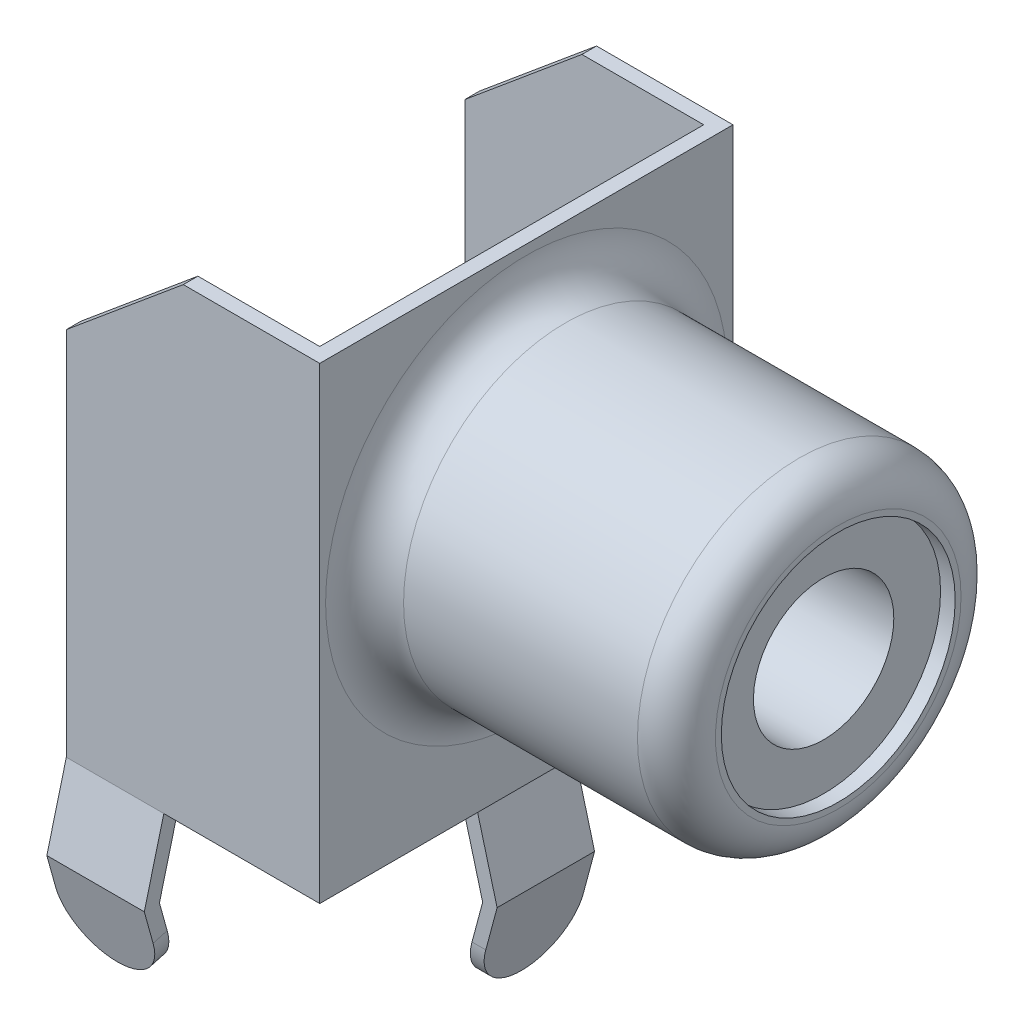
SolidWorks part; units mm, degrees
ref_plane "Front" through (0, 0, 0) normal (0, 0, 1) x (1, 0, 0)
ref_plane "Top" through (0, 0, 0) normal (0, 1, 0) x (1, 0, 0)
ref_plane "Right" through (0, 0, 0) normal (1, 0, 0) x (0, 0, -1)
sketch "Sketch1" plane through (0, 0, 0) normal (1, 0, 0) x (0, 0, -1)
  line L0 (0, 0) -> (0, 17.5966) construction
  line L1 (5.3, 5.4) -> (-5.3, 5.4)
  line L2 (-5.3, 5.4) -> (-5.3, -6.6)
  line L3 (-5.3, -6.6) -> (5.3, -6.6)
  line L4 (5.3, 5.4) -> (5.3, -6.6)
  line L5 (1.25, -9.55) -> (1.25, -6.6)
  line L6 (-1.25, -9.55) -> (-1.25, -6.6)
  line L7 (-5.3, -6.6) -> (-5.8, -8.5327)
  line L8 (4.3187, -10.8) -> (-5.8789, -10.8) construction
  line L9 (-5.8, -8.5327) -> (-5.2407, -10.55)
  line L10 (-5.2407, -10.55) -> (-4.8794, -10.4498)
  line L11 (-4.8794, -10.4498) -> (-5.4118, -8.5294)
  line L12 (-5.4118, -8.5294) -> (-4.9127, -6.6)
  line L13 (5.4118, -8.5294) -> (4.9127, -6.6)
  line L14 (4.8794, -10.4498) -> (5.4118, -8.5294)
  line L15 (5.2407, -10.55) -> (4.8794, -10.4498)
  line L16 (5.8, -8.5327) -> (5.2407, -10.55)
  line L17 (5.3, -6.6) -> (5.8, -8.5327)
  line L18 (-4.9127, -6.6) -> (-4.9127, 5.4)
  line L19 (4.9127, -6.6) -> (4.9127, 5.4)
  line L20 (-0.65, -9.8) -> (0.65, -9.8)
  line L21 (0.65, -9.8) -> (0.65, -5.455)
  line L22 (0.65, -5.455) -> (1.625, -4.48)
  line L23 (1.625, -4.48) -> (1.625, -1.6)
  line L24 (1.625, -1.6) -> (-1.625, -1.6)
  line L25 (0, 0) -> (0, -11.7366) construction
  line L26 (-1.625, -4.48) -> (-1.625, -1.6)
  line L27 (-0.65, -5.455) -> (-1.625, -4.48)
  line L28 (-0.65, -9.8) -> (-0.65, -5.455)
  line L29 (-4.8794, -10.4498) -> (4.8794, -10.4498)
  line L30 (-1.625, -1.975) -> (1.625, -1.975)
  circle A0 centre (0, 0) radius 1.8
  circle A1 centre (0, 0) radius 4.15
  arc A2 (-1.25, -9.55) -> (1.25, -9.55) centre (0, -9.55) ccw
  circle A3 centre (0, 0) radius 3.8125
  circle A4 centre (0, 0) radius 3.775
  circle A5 centre (0, 0) radius 3
  point P10 (0, 5.4)
  point P11 (0, -6.6)
  point P38 (0, -1.6)
  dimension "D1" = 3.6
  dimension "D2" = 8.3
  dimension "D7" = 4.2
  dimension "D17" = 7.625
  dimension "D19" = 6
  dimension "D3" = 10.6
  dimension "D4" = 12
  dimension "D5" = 6.6
  dimension "D6" = 2.5
  dimension "D8" = 3.95
  dimension "D9" = 0.375
  dimension "D10" = 0.375
  dimension "D11" = 11.6
  dimension "D12" = 150
  dimension "D13" = 1.6
  dimension "D14" = 3.25
  dimension "D15" = 2.88
  dimension "D16" = 135
  dimension "D20" = 0.375
  dimension "D21" = 1.3
  dimension "D22" = 3.2
  dimension "D18" = 0.375
sketch "Sketch2" plane through (0, 0, 0) normal (0, 0, 1) x (1, 0, 0)
  line L0 (0, 0) -> (0, 19.9245)
  line L1 (0, 19.9245) -> (6.5, 19.9245)
  line L2 (6.5, 19.9245) -> (6.5, 15.5349)
  line L3 (6.5, 15.5349) -> (14.5, 15.5349)
  line L4 (14.5, 15.5349) -> (14.5, 0)
  line L5 (14.125, 15.5349) -> (14.125, 0)
  line L6 (1.25, 19.9245) -> (1.25, 0)
  line L7 (6.5, -6.6) -> (7, -8.466)
  line L8 (7, -8.466) -> (6.4416, -10.55)
  line L9 (6.4416, -10.55) -> (6.1118, -10.4616)
  line L10 (6.1118, -10.4616) -> (6.6291, -8.5308)
  line L11 (6.6291, -8.5308) -> (6.1118, -6.6)
  line L12 (6.1118, -6.6) -> (6.5, -6.6)
  line L13 (0, -6.6) -> (0, -9.3)
  line L16 (2.5, -9.3) -> (2.5, -6.6)
  line L17 (2.5, -6.6) -> (0, -6.6)
  arc A0 (0, -9.3) -> (2.5, -9.3) centre (1.25, -9.3) ccw
  dimension "D11" = 2.5
  dimension "D1" = 6.5
  dimension "D2" = 14.5
  dimension "D3" = 0.375
  dimension "D4" = 1.25
  dimension "D5" = 6.6
  dimension "D6" = 0.5
  dimension "D7" = 0.375
  dimension "D8" = 3.95
  dimension "D9" = 6.5
  dimension "D10" = 150
  dimension "D12" = 2.7
ref_axis "Axis1" through (-80.9, 0, 0) along (1, 0, 0)
sketch "Sketch22" plane through (0, 0, 0) normal (1, 0, 0) x (0, 0, -1)
  line L1 (5.3, 5.4) -> (5.3, -6.6) construction
  line L2 (5.3, 5.4) -> (-5.3, 5.4) construction
  line L3 (-5.3, 5.4) -> (-5.3, -6.6) construction
  line L4 (-5.3, -6.6) -> (-5.8, -8.5327) construction
  line L5 (5.3, 5.4) -> (5.3, -6.6)
  line L6 (5.3, 5.4) -> (-5.3, 5.4)
  line L7 (-5.3, 5.4) -> (-5.3, -6.6)
  line L8 (-5.8, -8.5327) -> (-5.2407, -10.55) construction
  line L9 (-5.2407, -10.55) -> (-4.8794, -10.4498) construction
  line L10 (-4.8794, -10.4498) -> (4.8794, -10.4498) construction
  line L11 (5.2407, -10.55) -> (4.8794, -10.4498) construction
  line L12 (5.8, -8.5327) -> (5.2407, -10.55) construction
  line L13 (5.3, -6.6) -> (5.8, -8.5327) construction
  line L14 (-5.3, -6.6) -> (-5.8, -8.5327)
  line L15 (-5.8, -8.5327) -> (-5.2407, -10.55)
  line L16 (-5.2407, -10.55) -> (-4.8794, -10.4498)
  line L17 (-4.8794, -10.4498) -> (4.8794, -10.4498)
  line L18 (5.2407, -10.55) -> (4.8794, -10.4498)
  line L19 (5.8, -8.5327) -> (5.2407, -10.55)
  line L20 (5.3, -6.6) -> (5.8, -8.5327)
extrude "Extrude15" add sketch "Sketch22" along normal up to vertex (6.5 mm away) up to point (6.5, 15.5349, 0)
shell "Shell1" thickness 0.375 removed face at (3.25, 5.4, 0) removed face at (3.25, -10.4498, 0) removed face at (0, -6.1465, 0)
sketch "Sketch23" plane through (6.5, 0, 0) normal (1, 0, 0) x (0, 0, -1)
  line L0 (5.4118, -8.5294) -> (4.9127, -6.6) construction
  line L1 (4.8794, -10.4498) -> (5.4118, -8.5294) construction
  line L2 (-4.8794, -10.4498) -> (4.8794, -10.4498) construction
  line L3 (-4.8794, -10.4498) -> (-5.4118, -8.5294) construction
  line L4 (-5.4118, -8.5294) -> (-4.9127, -6.6) construction
  line L5 (-5.3, -6.6) -> (5.3, -6.6) construction
  line L6 (5.4118, -8.5294) -> (4.9127, -6.6)
  line L7 (4.8794, -10.4498) -> (5.4118, -8.5294)
  line L8 (-4.8794, -10.4498) -> (4.8794, -10.4498)
  line L9 (-4.8794, -10.4498) -> (-5.4118, -8.5294)
  line L10 (-5.4118, -8.5294) -> (-4.9127, -6.6)
  line L11 (-4.9127, -6.6) -> (4.9127, -6.6)
extrude "Cut-Extrude1" cut sketch "Sketch23" against normal through all
sketch "Sketch24" plane through (0, 0, 0) normal (0, 0, 1) x (1, 0, 0)
  line L0 (6.6291, -8.5308) -> (6.1118, -6.6) construction
  line L1 (6.1118, -6.6) -> (6.5, -6.6) construction
  line L2 (6.5, -6.6) -> (7, -8.466) construction
  line L3 (7, -8.466) -> (6.4416, -10.55) construction
  line L4 (6.1118, -10.4616) -> (6.6291, -8.5308) construction
  line L6 (6.6291, -8.5308) -> (6.1118, -6.6)
  line L7 (6.1118, -6.6) -> (6.5, -6.6)
  line L8 (6.5, -6.6) -> (7, -8.466)
  line L9 (7, -8.466) -> (6.2097, -11.4156)
  line L10 (5.8632, -11.3894) -> (6.6291, -8.5308)
  line L11 (6.2097, -11.4156) -> (5.8632, -11.3894)
extrude "Extrude16" add sketch "Sketch24" along normal up to vertex (1.25 mm away) and the other way up to vertex (1.25 mm away) separate body up to point (0, -9.55, 1.25) other way up to point (0, -9.55, -1.25)
sketch "Sketch28" plane through (0, -2.1022, 7.5828) normal (0, -0.2672, 0.9637) x (1, 0, 0)
  line L1 (2.5, -6.673) -> (8.1659, -6.673)
  line L3 (0, -6.3601) -> (0, -8.962)
  line L4 (2.5, -6.3601) -> (0, -6.3601)
  line L5 (2.5, -8.962) -> (2.5, -6.3601)
  line L6 (0, -6.673) -> (0, -7.5164)
  line L7 (8.1659, -6.673) -> (8.1659, -10.1113)
  line L8 (2.5, -7.5164) -> (2.5, -6.673)
  line L9 (8.1659, -10.1113) -> (-0.8346, -10.1113)
  line L10 (-0.8346, -10.1113) -> (-0.8346, -6.673)
  line L11 (-0.8346, -6.673) -> (0, -6.673)
  arc A1 (0, -7.5164) -> (2.5, -7.5164) centre (1.25, -7.5164) ccw
  ellipse E1 centre (1.25, -8.962) end of major axis (2.5, -8.962) minor radius 1.2046 (0, -8.962) -> (2.5, -8.962) ccw
  dimension "D1" = 0
extrude "Cut-Extrude5" cut sketch "Sketch28" against normal up to surface (0.375 mm away)
sketch "Sketch30" plane through (0, -2.1022, -7.5828) normal (0, -0.2672, -0.9637) x (-1, 0, 0)
  line L0 (-2.5, -6.673) -> (-6.7238, -6.673)
  line L2 (-6.5, -8.7664) -> (0, -8.7664) construction
  line L3 (0, -8.962) -> (0, -6.3601)
  line L4 (0, -6.3601) -> (-2.5, -6.3601)
  line L5 (-2.5, -6.3601) -> (-2.5, -8.962)
  line L6 (0, -7.5164) -> (0, -6.673)
  line L7 (-6.7238, -6.673) -> (-6.7238, -9.6775)
  line L8 (-2.5, -6.673) -> (-2.5, -7.5164)
  line L9 (-2.5, -8.7664) -> (0, -8.7664) construction
  line L10 (-6.7238, -9.6775) -> (1.0431, -9.6775)
  line L11 (1.0431, -9.6775) -> (1.0431, -6.673)
  line L12 (1.0431, -6.673) -> (0, -6.673)
  arc A0 (-2.5, -7.5164) -> (0, -7.5164) centre (-1.25, -7.5164) ccw
  ellipse E1 centre (-1.25, -8.962) end of major axis (-2.5, -8.962) minor radius 1.2046 (-2.5, -8.962) -> (0, -8.962) ccw
  dimension "D1" = 0
extrude "Cut-Extrude6" cut sketch "Sketch30" against normal up to surface (0.375 mm away)
sketch "Sketch31" plane through (6.5, 0, 0) normal (1, 0, 0) x (0, 0, -1)
  line L0 (5.2407, -10.55) -> (4.8794, -10.4498) construction
  line L1 (5.8, -8.5327) -> (5.2407, -10.55) construction
  line L2 (5.3, -6.6) -> (5.8, -8.5327) construction
  line L3 (5.4118, -8.5294) -> (4.9127, -6.6) construction
  line L4 (4.8794, -10.4498) -> (5.4118, -8.5294) construction
  line L5 (-5.8, -8.5327) -> (-5.2407, -10.55) construction
  line L6 (-5.2407, -10.55) -> (-4.8794, -10.4498) construction
  line L7 (-4.8794, -10.4498) -> (-5.4118, -8.5294) construction
  line L8 (-5.3, -6.6) -> (5.3, -6.6) construction
  line L9 (-5.4118, -8.5294) -> (-4.9127, -6.6) construction
  line L10 (-5.3, -6.6) -> (-5.8, -8.5327) construction
  line L11 (5.2407, -10.55) -> (4.8794, -10.4498)
  line L12 (5.8, -8.5327) -> (5.2407, -10.55)
  line L13 (5.3, -6.6) -> (5.8, -8.5327)
  line L14 (5.4118, -8.5294) -> (4.9127, -6.6)
  line L15 (4.8794, -10.4498) -> (5.4118, -8.5294)
  line L16 (-5.8, -8.5327) -> (-5.2407, -10.55)
  line L17 (-5.2407, -10.55) -> (-4.8794, -10.4498)
  line L18 (-4.8794, -10.4498) -> (-5.4118, -8.5294)
  line L19 (-5.3, -6.6) -> (-4.9127, -6.6)
  line L20 (-5.4118, -8.5294) -> (-4.9127, -6.6)
  line L21 (-5.3, -6.6) -> (-5.8, -8.5327)
  line L22 (4.9127, -6.6) -> (5.3, -6.6)
extrude "Cut-Extrude7" cut sketch "Sketch31" against normal blind 4
sketch "Sketch32" plane through (6.5, 1.6977, 0) normal (1, 0, 0) x (0, 0, -1)
  arc A0 (-1.25, -11.2477) -> (1.25, -11.2477) centre (0, -11.2477) ccw construction
  arc A1 (-1.25, -11.2477) -> (1.25, -11.2477) centre (0, -11.2477) ccw
extrude "Cut-Extrude8" cut sketch "Sketch32" against normal through all and the other way through all flip side to cut
sketch "Sketch33" plane through (6.5, 0, 0) normal (1, 0, 0) x (0, 0, -1)
  circle A0 centre (0, 0) radius 3.8125 construction
  circle A1 centre (0, 0) radius 3.8125
extrude "Cut-Extrude9" cut sketch "Sketch33" against normal through all
sketch "Sketch34" plane through (6.5, 0, 0) normal (1, 0, 0) x (0, 0, -1)
  circle A0 centre (0, 0) radius 1.8 construction
  circle A1 centre (0, 0) radius 3.775 construction
  circle A2 centre (0, 0) radius 1.8
  circle A3 centre (0, 0) radius 3.775
extrude "Extrude17" add sketch "Sketch34" along normal up to vertex (7.625 mm away) separate body up to point (14.125, 15.5349, 0)
sketch "Sketch35" plane through (6.5, 0, 0) normal (1, 0, 0) x (0, 0, -1)
  circle A0 centre (0, 0) radius 4.15 construction
  circle A1 centre (0, 0) radius 3.775 construction
  circle A2 centre (0, 0) radius 4.15
  circle A3 centre (0, 0) radius 3.775
extrude "Extrude18" add sketch "Sketch35" along normal up to vertex (8 mm away) up to point (14.5, 15.5349, 0)
sketch "Sketch36" plane through (14.125, 0, 0) normal (1, 0, 0) x (0, 0, -1)
  circle A0 centre (0, 0) radius 3 construction
  circle A1 centre (0, 0) radius 3
  circle A2 centre (0, 0) radius 3.775 construction
  circle A3 centre (0, 0) radius 3.775
extrude "Extrude19" add sketch "Sketch36" along normal up to vertex (0.375 mm away) up to point (14.5, 15.5349, 0)
fillet "Fillet5" radius 1 1 edges at (14.5, 0, -4.15)
fillet "Fillet6" radius 1 1 edges at (6.5, 0, 4.15)
sketch "Sketch38" plane through (0, 0, 0) normal (0, 0, 1) x (1, 0, 0)
  line L0 (6.5, 15.5349) -> (6.5, -20.6951) construction
  line L1 (1.25, -11.6) -> (1.25, -1.6)
  line L2 (1.25, -1.6) -> (6.5, -1.6)
  line L3 (1.625, -1.975) -> (6.5, -1.975)
  line L4 (1.625, -11.6) -> (1.625, -1.975)
  line L5 (6.5, -1.975) -> (6.5, -1.6)
  line L6 (1.25, -11.6) -> (1.625, -11.6)
  dimension "D1" = 1.6
  dimension "D2" = 1.25
  dimension "D3" = 10
  dimension "D4" = 0.375
extrude "Extrude21" add sketch "Sketch38" along normal mid plane 3.25
sketch "Sketch39" plane through (1.25, 0, 0) normal (-1, 0, 0) x (0, 0, 1)
  line L3 (0.65, -5.455) -> (1.625, -4.48) construction
  line L4 (-1.625, -6.6) -> (1.625, -6.6) construction
  line L5 (-1.25, -6.6) -> (-4.925, -6.6) construction
  line L6 (-0.65, -5.455) -> (-1.625, -4.48) construction
  line L7 (-0.65, -10.8) -> (-0.65, -5.455)
  line L8 (0.65, -10.8) -> (-0.65, -10.8)
  line L9 (0.65, -10.8) -> (0.65, -5.455)
  line L10 (0.65, -5.455) -> (1.625, -4.48)
  line L11 (-1.625, -1.6) -> (-1.625, -11.6) construction
  line L12 (1.625, -1.6) -> (1.625, -11.6) construction
  line L13 (-0.65, -5.455) -> (-1.625, -4.48)
  line L15 (1.625, -4.48) -> (1.625, -11.6)
  line L16 (-1.625, -4.48) -> (-1.625, -11.6)
  line L18 (1.625, -11.6) -> (-1.625, -11.6) construction
  line L21 (1.625, -11.6) -> (-1.625, -11.6)
  dimension "D1" = 4.2
extrude "Cut-Extrude10" cut sketch "Sketch39" against normal blind 0.375
sketch "Sketch40" plane through (0, 0, 0) normal (0, 0, 1) x (1, 0, 0)
  line L0 (3, 5.4) -> (0, 2.9)
  line L1 (6.5, 5.4) -> (0, 5.4) construction
  line L2 (0, -6.6) -> (0, 5.4) construction
  line L3 (0, 2.9) -> (0, 5.4)
  line L4 (0, 5.4) -> (3, 5.4)
  dimension "D1" = 2.5
  dimension "D2" = 3
extrude "Extrude22" cut sketch "Sketch40" against normal through all and the other way through all
